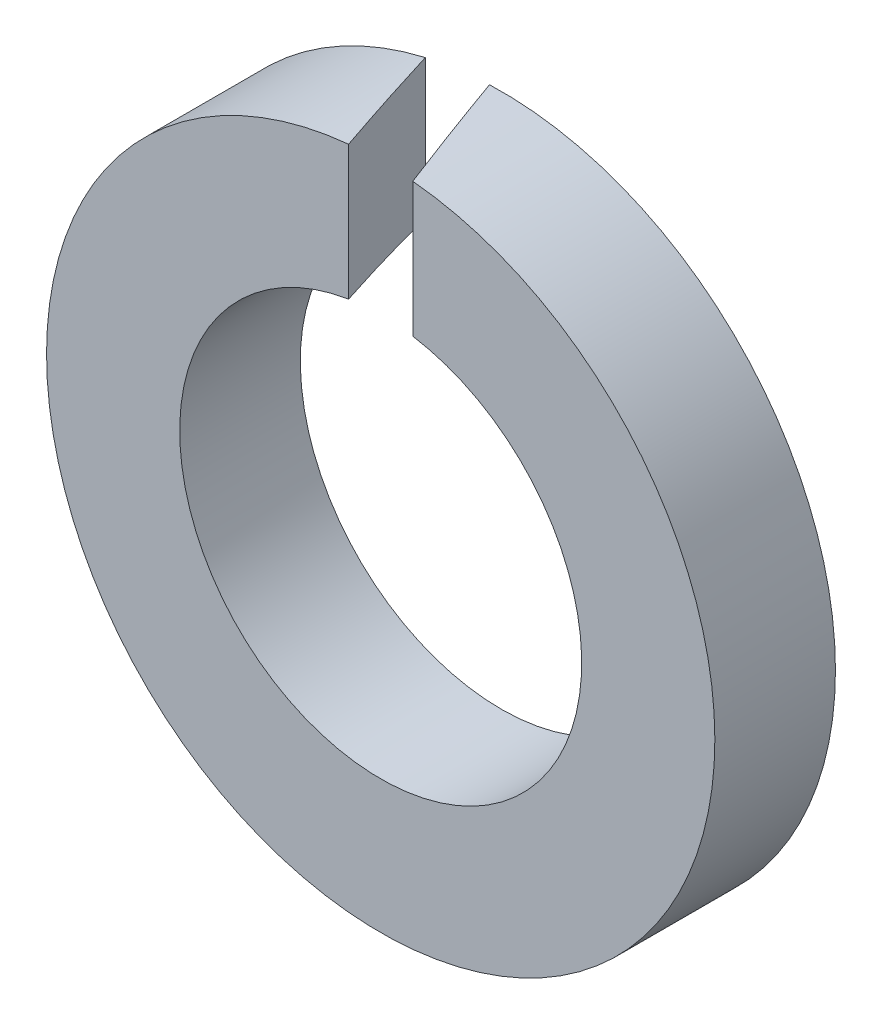
SolidWorks part; units mm, degrees
ref_plane "Front" through (0, 0, 0) normal (0, 0, 1) x (1, 0, 0)
ref_plane "Top" through (0, 0, 0) normal (0, 1, 0) x (1, 0, 0)
ref_plane "Right" through (0, 0, 0) normal (1, 0, 0) x (0, 0, -1)
sketch "Sketch1" plane through (0, 0, 0) normal (0, 0, 1) x (1, 0, 0)
  circle A0 centre (0, 0) radius 13.3
  circle A1 centre (0, 0) radius 8
  dimension "d" = 16
  dimension "b" = 5.3
extrude "Base-Extrude" add sketch "Sketch1" against normal blind 4.8
sketch "Sketch2" plane through (-3.0216, 0, -2.3453) normal (0, 1, 0) x (0, 0, -1)
  line L0 (0.7451, -1.8968) -> (-7.0218, -4.7237) construction
  line L1 (-2.3453, -1.7446) -> (2.4547, 0.0024)
  line L2 (2.4547, -16.3216) -> (2.4547, 10.2784) construction
  line L5 (-2.3453, -4.2986) -> (2.4547, -2.5516)
  line L6 (-2.3453, -1.7446) -> (-2.3453, -4.2986)
  line L7 (2.4547, 0.0024) -> (2.4547, -2.5516)
  line L8 (-2.3453, 4.9784) -> (-2.3453, -11.0216) construction
  line L10 (-2.3453, 10.2784) -> (-2.3453, -16.3216) construction
  dimension "D1" = 70
  dimension "m" = 2.4
  dimension "D3" = 2.4
extrude "Cut-Extrude1" cut sketch "Sketch2" along normal through all
